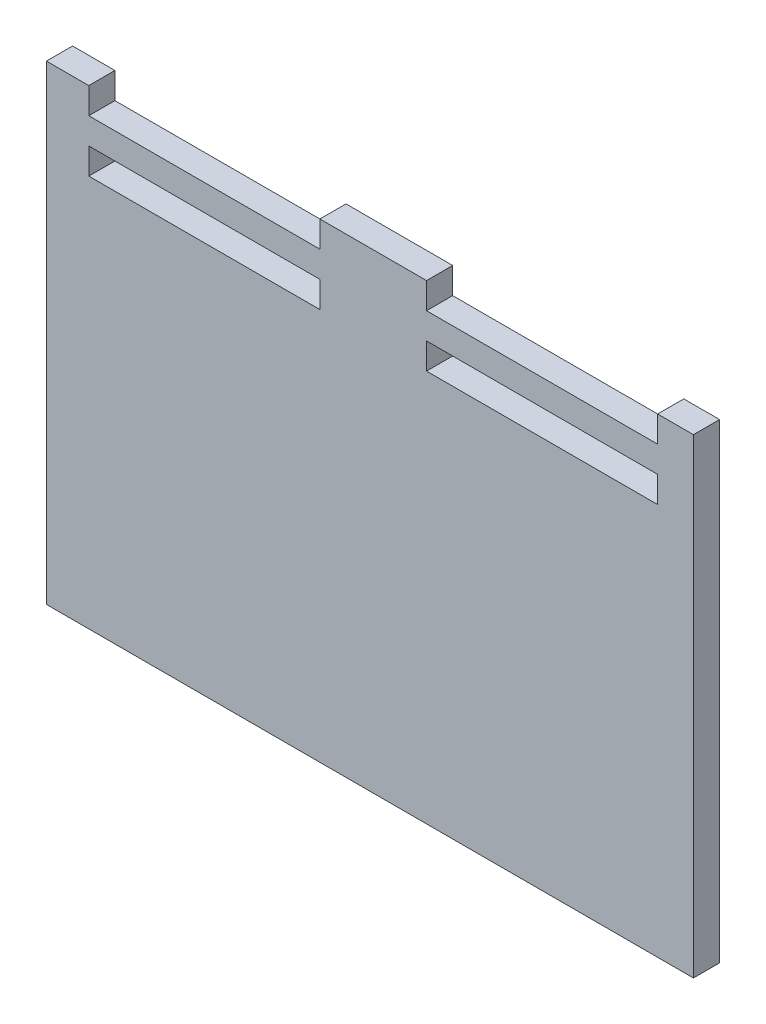
SolidWorks part; units mm, degrees
ref_plane "Front Plane" through (0, 0, 0) normal (0, 0, 1) x (1, 0, 0)
ref_plane "Top Plane" through (0, 0, 0) normal (0, 1, 0) x (1, 0, 0)
ref_plane "Right Plane" through (0, 0, 0) normal (1, 0, 0) x (0, 0, -1)
sketch "Sketch1" plane through (0, 0, 0) normal (0, 0, 1) x (1, 0, 0)
  line L1 (0, 0) -> (304.8, 0)
  line L2 (0, 0) -> (0, 228.6)
  line L3 (0, 228.6) -> (304.8, 228.6)
  line L4 (304.8, 0) -> (304.8, 228.6)
  dimension "D1" = 304.8
  dimension "D2" = 228.6
extrude "Boss-Extrude1" add sketch "Sketch1" along normal blind 12.7
sketch "Sketch6" plane through (0, 0, 12.7) normal (0, 0, 1) x (1, 0, 0)
  line L0 (0, 114.3) -> (304.8, 114.3) construction
  line L1 (0, 228.6) -> (0, 0) construction
  line L2 (304.8, 0) -> (304.8, 228.6) construction
sketch "Sketch7" plane through (0, 0, 12.7) normal (0, 0, 1) x (1, 0, 0)
  line L1 (14.224, 228.6) -> (126.492, 228.6)
  line L2 (14.224, 228.6) -> (14.224, 215.9)
  line L3 (14.224, 215.9) -> (126.492, 215.9)
  line L4 (0, 228.6) -> (0, 0)
  line L5 (0, 0) -> (304.8, 0)
  line L6 (304.8, 0) -> (304.8, 228.6)
  line L7 (304.8, 228.6) -> (0, 228.6)
  line L8 (0, 228.6) -> (0, 0)
  line L9 (0, 0) -> (304.8, 0)
  line L10 (304.8, 0) -> (304.8, 228.6)
  line L11 (304.8, 228.6) -> (0, 228.6)
  line L12 (126.492, 228.6) -> (126.492, 215.9)
  line L13 (178.308, 228.6) -> (290.576, 228.6)
  line L14 (178.308, 228.6) -> (178.308, 215.9)
  line L15 (178.308, 215.9) -> (290.576, 215.9)
  line L16 (290.576, 228.6) -> (290.576, 215.9)
  line L17 (14.224, 203.2) -> (126.492, 203.2)
  line L18 (14.224, 203.2) -> (14.224, 190.5)
  line L19 (14.224, 190.5) -> (126.492, 190.5)
  line L20 (126.492, 203.2) -> (126.492, 190.5)
  line L21 (178.308, 203.2) -> (290.576, 203.2)
  line L22 (178.308, 203.2) -> (178.308, 190.5)
  line L23 (178.308, 190.5) -> (290.576, 190.5)
  line L24 (290.576, 203.2) -> (290.576, 190.5)
  point P20 (70.358, 203.2)
  line M17 (304.8, 228.6) -> (0, 228.6)
  dimension "D2" = 14.224
  dimension "D3" = 112.268
  dimension "D4" = 112.268
  dimension "D5" = 14.224
  dimension "D6" = 12.7
  dimension "D7" = 12.7
  dimension "D8" = 12.7
  dimension "D9" = 112.268
  dimension "D10" = 112.268
  dimension "D11" = 12.7
  dimension "D12" = 12.7
  dimension "D1" = 0
extrude "Cut-Extrude2" cut sketch "Sketch7" against normal blind 12.7 contours L12 L2 L3 M17 | L15 L16 L13 L14 | L18 L17 L20 L19 | L22 L21 L24 L23 region at (70.358, 222.25, 12.7)
sketch "Sketch8" plane through (0, 0, 12.7) normal (0, 0, 1) x (1, 0, 0)
  line L1 (304.8, 228.6) -> (307.975, 228.6)
  line L2 (304.8, 228.6) -> (304.8, 0)
  line L3 (304.8, 0) -> (307.975, 0)
  line L4 (307.975, 228.6) -> (307.975, 0)
  line L5 (0, 228.6) -> (-6.35, 228.6)
  line L6 (0, 228.6) -> (0, 0)
  line L7 (0, 0) -> (-6.35, 0)
  line L8 (-6.35, 228.6) -> (-6.35, 0)
  line L12 (290.576, 215.9) -> (178.308, 215.9)
  line L13 (178.308, 215.9) -> (178.308, 228.6)
  line L14 (178.308, 228.6) -> (126.492, 228.6)
  line L15 (126.492, 228.6) -> (126.492, 215.9)
  line L16 (126.492, 215.9) -> (14.224, 215.9)
  line L17 (14.224, 215.9) -> (14.224, 228.6)
  line L18 (14.224, 228.6) -> (0, 228.6)
  line L19 (0, 228.6) -> (0, 0)
  line L20 (0, 0) -> (304.8, 0)
  line L21 (304.8, 0) -> (304.8, 228.6)
  line L22 (304.8, 228.6) -> (290.576, 228.6)
  line L23 (290.576, 228.6) -> (290.576, 215.9)
  line L24 (290.576, 215.9) -> (178.308, 215.9)
  line L25 (178.308, 215.9) -> (178.308, 228.6)
  line L26 (178.308, 228.6) -> (126.492, 228.6)
  line L27 (126.492, 228.6) -> (126.492, 215.9)
  line L28 (126.492, 215.9) -> (14.224, 215.9)
  line L29 (14.224, 215.9) -> (14.224, 228.6)
  line L30 (14.224, 228.6) -> (0, 228.6)
  line L31 (0, 228.6) -> (0, 0)
  line L32 (0, 0) -> (304.8, 0)
  line L33 (304.8, 0) -> (304.8, 228.6)
  line L34 (304.8, 228.6) -> (290.576, 228.6)
  line L35 (290.576, 228.6) -> (290.576, 215.9)
  line M22 (0, 228.6) -> (0, 0)
  line M24 (304.8, 0) -> (304.8, 228.6)
  dimension "D2" = 6.35
  dimension "D3" = 3.175
  dimension "D1" = 0
extrude "Boss-Extrude2" add sketch "Sketch8" against normal blind 12.7 contours L5 L8 L7 M22 | L4 L1 L3 M24 region at (306.3875, 114.3, 12.7) region at (-3.175, 114.3, 12.7)
